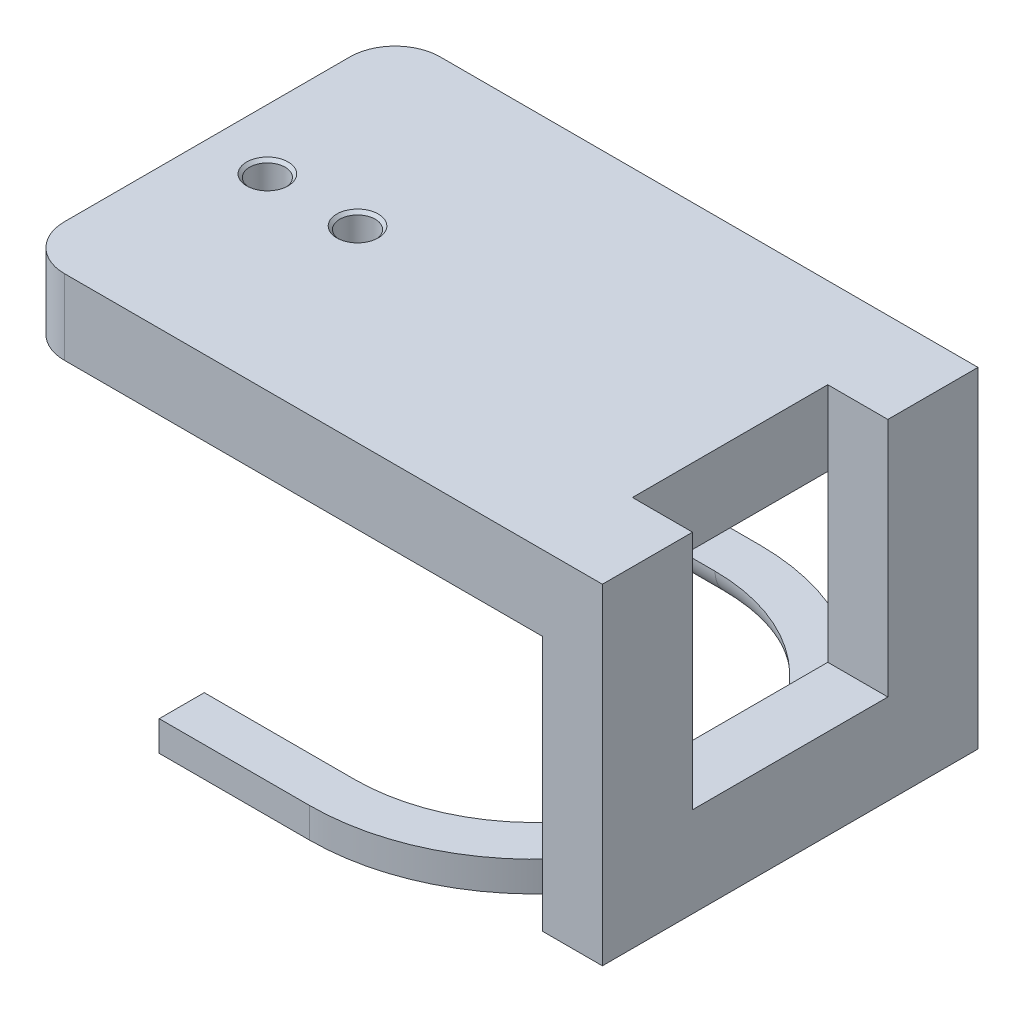
SolidWorks part; units mm, degrees
ref_plane "Front Plane" through (0, 0, 0) normal (0, 0, 1) x (1, 0, 0)
ref_plane "Top Plane" through (0, 0, 0) normal (0, 1, 0) x (1, 0, 0)
ref_plane "Right Plane" through (0, 0, 0) normal (1, 0, 0) x (0, 0, -1)
sketch "Sketch1" plane through (0, 0, 0) normal (0, 1, 0) x (1, 0, 0)
  line L1 (0, 0) -> (44.196, 0)
  line L2 (0, 0) -> (0, 31.75)
  line L3 (0, 31.75) -> (44.196, 31.75)
  line L4 (44.196, 0) -> (44.196, 31.75)
  dimension "D1" = 44.196
  dimension "D2" = 31.75
extrude "Boss-Extrude1" add sketch "Sketch1" along normal blind 6.35
hole_wizard "Ø3.0mm Dowel Hole1" positions "Sketch5" profile "Sketch4" hole size "Ø3.0" standard "ISO" end condition through all
sketch "Sketch5" plane through (0, 6.35, 0) normal (0, 1, 0) x (1, 0, 0)
  line L0 (0, 0) -> (44.196, 0) construction
  line L1 (0, 31.75) -> (0, 0) construction
  point P0 (5.08, 15.875)
  point P2 (12.7, 15.875)
  dimension "D1" = 15.875
  dimension "D2" = 5.08
  dimension "D3" = 7.62
sketch "Sketch4" plane through (5.08, 6.35, -15.875) normal (1, 0, 0) x (0, 0, 1)
  line L0 (0, 0) -> (0, 6.35)
  line L1 (0, 6.35) -> (1.5, 6.35)
  line L2 (1.5, 6.35) -> (1.5, 0)
  line L5 (1.5, 0) -> (0, 0)
  line L11 (0, -6.35) -> (0, 107.95) construction
  dimension "Thru Hole Dia." = 3
  dimension "Thru Hole Depth" = 6.35
chamfer "Chamfer1" distance 0.254 angle 45 4 edges at (12.7, 6.35, -14.375) (5.08, 6.35, -14.375) (5.08, 0, -14.375) (12.7, 0, -14.375)
fillet "Fillet2" radius 3.81 2 edges at (0, 3.175, 0) (0, 3.175, -31.75)
sketch "Sketch6" plane through (44.196, 0, 0) normal (1, 0, 0) x (0, 0, -1)
  line L0 (0, 6.35) -> (0, -21.59)
  line L1 (31.75, 6.35) -> (31.75, -21.59)
  line L2 (31.75, -21.59) -> (0, -21.59)
  line L3 (0, 6.35) -> (7.62, 6.35)
  line L4 (0, 6.35) -> (31.75, 6.35) construction
  line L5 (7.62, 6.35) -> (7.62, -13.97)
  line L6 (7.62, -13.97) -> (24.13, -13.97)
  line L7 (24.13, -13.97) -> (24.13, 6.35)
  line L8 (24.13, 6.35) -> (31.75, 6.35)
  dimension "D1" = 7.62
  dimension "D2" = 7.62
  dimension "D3" = 27.94
  dimension "D4" = 7.62
extrude "Boss-Extrude4" add sketch "Sketch6" along normal blind 5.08
sketch "Sketch8" plane through (0, -21.59, 0) normal (0, -1, 0) x (1, 0, 0)
  line L2 (27.686, 0.635) -> (14.986, 0.635)
  line L3 (27.686, -32.385) -> (14.986, -32.385)
  line L4 (44.196, 0) -> (44.196, -31.75) construction
  arc A0 (27.686, -32.385) -> (27.686, 0.635) centre (27.686, -15.875) ccw
  dimension "D1" = 16.51
  dimension "D2" = 16.51
  dimension "D3" = 12.7
  dimension "D4" = 12.7
extrude "Extrude-Thin1" add sketch "Sketch8" against normal blind 2.54 separate body thin thin type two direction wall 1.27 second wall 2.54
fillet "Fillet3" radius 2.54 3 edges at (21.336, -21.59, -0.635) (21.336, -21.59, -31.115) (42.926, -21.59, -15.875)
